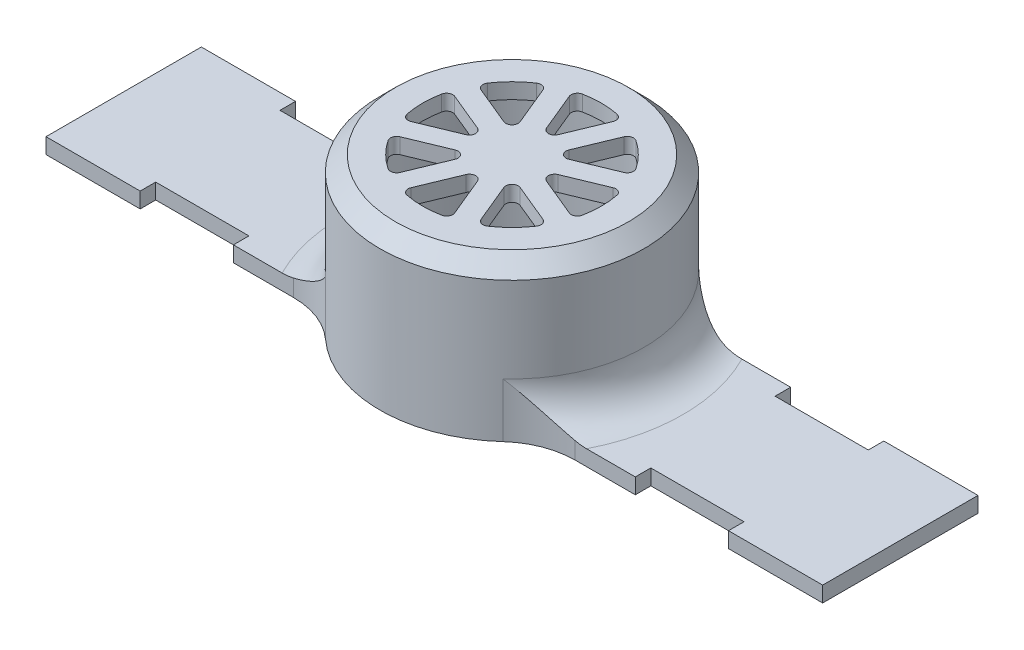
SolidWorks part; units mm, degrees
ref_plane "前视基准面" through (0, 0, 0) normal (0, 0, 1) x (1, 0, 0)
ref_plane "上视基准面" through (0, 0, 0) normal (0, 1, 0) x (1, 0, 0)
ref_plane "右视基准面" through (0, 0, 0) normal (1, 0, 0) x (0, 0, -1)
sketch "草图1" plane through (0, 0, 0) normal (0, 1, 0) x (1, 0, 0)
  line L1 (-50, 10) -> (50, 10)
  line L2 (-50, 10) -> (-50, -10)
  line L3 (-50, -10) -> (50, -10)
  line L4 (50, 10) -> (50, -10)
  line L5 (-50, 10) -> (50, -10) construction
  line L6 (-50, -10) -> (50, 10) construction
  point P0 (0, 0)
  dimension "D1" = 50
  dimension "D2" = 20
extrude "凸台-拉伸1" add sketch "草图1" along normal blind 2
sketch "草图2" plane through (0, 0, 0) normal (0, 1, 0) x (1, 0, 0)
  circle A0 centre (0, 0) radius 17
  dimension "D1" = 34
extrude "凸台-拉伸2" add sketch "草图2" along normal blind 20
sketch "草图3" plane through (0, 0, 0) normal (0, 1, 0) x (1, 0, 0)
  circle A0 centre (0, 0) radius 15
  dimension "D1" = 30
extrude "切除-拉伸1" cut sketch "草图3" along normal offset from surface (18 mm away) 2 up to face at (0, 20, 17)
sketch "草图4" plane through (0, 0, 0) normal (0, 1, 0) x (1, 0, 0)
  line L0 (-31.8739, -10) -> (-31.8739, 10) construction
  line L1 (-50, -10) -> (-13.7477, -10) construction
  line L2 (-13.7477, 10) -> (-50, 10) construction
  line L4 (-25.8739, -8) -> (-37.8739, -8)
  line L5 (-25.8739, -8) -> (-25.8739, -10)
  line L6 (-25.8739, -10) -> (-37.8739, -10)
  line L7 (-37.8739, -8) -> (-37.8739, -10)
  line L8 (-25.8739, -8) -> (-37.8739, -10) construction
  line L9 (-25.8739, -10) -> (-37.8739, -8) construction
  point P6 (-31.8739, -9)
  dimension "D1" = 2
  dimension "D2" = 12
extrude "切除-拉伸3" cut sketch "草图4" along normal up to next
mirror "镜向1" about plane through (0, 0, 0) normal (0, 0, 1) of "切除-拉伸3"
mirror "镜向2" about plane through (0, 0, 0) normal (1, 0, 0) of "镜向1"
fillet "圆角1" radius 10 4 edges at (-13.7477, 1, -10) (13.7477, 1, -10) (13.7477, 1, 10) (-13.7477, 1, 10)
fillet "圆角2" radius 5 2 edges at (17, 2, 0) (-17, 2, 0)
chamfer "倒角1" distance 2 angle 45 2 edges at (0, 18, 15) (0, 20, 17)
sketch "草图5" plane through (0, 18, 0) normal (0, -1, 0) x (1, 0, 0)
  line L0 (-4.4009, 10.6246) -> (0, 0) construction
  line L1 (0, 0) -> (4.4009, 10.6246) construction
  line L2 (-2.814, 10.1907) -> (-0.7391, 5.1814)
  line L3 (0.7391, 5.1814) -> (2.814, 10.1907)
  line L4 (0, 3.3971) -> (0, 0) construction
  circle A0 centre (0, 0) radius 11.5 construction
  arc A1 (-2.2301, 11.2817) -> (2.2301, 11.2817) centre (0, 0) cw
  arc A2 (2.814, 10.1907) -> (2.2301, 11.2817) centre (2.0749, 10.4969) ccw
  arc A3 (-0.7391, 5.1814) -> (0.7391, 5.1814) centre (0, 5.4876) ccw
  arc A4 (-2.2301, 11.2817) -> (-2.814, 10.1907) centre (-2.0749, 10.4969) ccw
  point P11 (3.1716, 11.054)
  point P17 (-3.1716, 11.054)
  point P18 (0, 0)
  dimension "D1" = 1.3
  dimension "D2" = 23
  dimension "D3" = 0.8
  dimension "D4" = 45
extrude "切除-拉伸4" cut sketch "草图5" against normal up to next
pattern_circular "阵列(圆周)1" count 8 over 360 about axis through (0, 20, 0) along (0, 1, 0) of "切除-拉伸4"
equation "\"拨盘中径\"= 64'8ball"
equation "\"球通道直径\"= 18"
equation "\"壁厚\"=2"
equation "\"加强筋高\"= 4"
equation "\"M3螺丝孔\"= 3.2"
equation "\"M3沉头孔\"= 6.5'杯头螺钉头高3mm"
equation "\"M3螺母孔\"= 6"
equation "\"电机杯直径\"= 30"
equation "\"线槽宽\"= 16"
equation "\"线槽高\"= 8"
equation "\"D2@草图1\"=\"线槽宽\"+\"壁厚\"*2"
equation "\"D1@凸台-拉伸1\"=\"壁厚\""
equation "\"D1@草图2\"=\"电机杯直径\"+\"壁厚\"*2"
equation "\"D1@凸台-拉伸2\"=22 -\"线槽高\"/2 + \"壁厚\""
equation "\"D1@草图3\"=\"电机杯直径\""
equation "\"D1@切除-拉伸1\"=\"壁厚\""
equation "\"D1@草图4\"=\"壁厚\""
